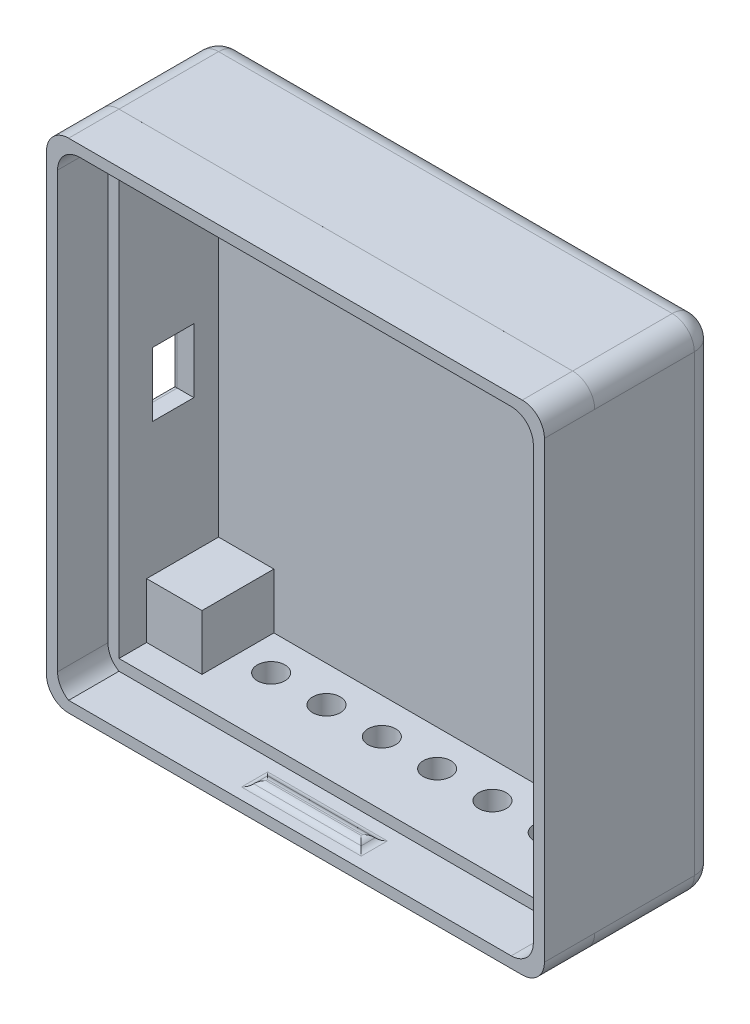
SolidWorks part; units mm, degrees
ref_plane "Piano frontale" through (0, 0, 0) normal (0, 0, 1) x (1, 0, 0)
ref_plane "Piano superiore" through (0, 0, 0) normal (0, 1, 0) x (1, 0, 0)
ref_plane "Piano destro" through (0, 0, 0) normal (1, 0, 0) x (0, 0, -1)
sketch "Schizzo2" plane through (0, 0, 0) normal (0, 0, 1) x (1, 0, 0)
  line L1 (0, 0) -> (45, 0)
  line L2 (0, 0) -> (0, 45)
  line L3 (0, 45) -> (45, 45)
  line L4 (45, 0) -> (45, 45)
  dimension "D1" = 45
  dimension "D2" = 45
extrude "Estrusione-Estrusione2" add sketch "Schizzo2" along normal blind 11
shell "Svuota1" thickness 2 removed face at (22.5, 22.5, 11)
fillet "Raccordo1" radius 2 4 edges at (45, 45, 5.5) (45, 0, 5.5) (0, 0, 5.5) (0, 45, 5.5)
fillet "Raccordo2" radius 2 8 edges at (44.4142, 0.5858, 0) (22.5, 0, 0) (0.5858, 0.5858, 0) (0, 22.5, 0) (0.5858, 44.4142, 0) (22.5, 45, 0) (44.4142, 44.4142, 0) (45, 22.5, 0)
sketch "Schizzo3" plane through (0, 0, 2) normal (0, 0, 1) x (1, 0, 0)
  line L0 (43, 43) -> (2, 43) construction
  line L1 (2, 43) -> (7, 43)
  line L2 (2, 43) -> (2, 38)
  line L3 (2, 38) -> (7, 38)
  line L4 (7, 43) -> (7, 38)
  line L5 (43, 43) -> (2, 43) construction
  dimension "D1" = 5
  dimension "D2" = 5
extrude "Estrusione-Estrusione3" add sketch "Schizzo3" along normal blind 6.5
sketch "Schizzo4" plane through (0, 0, 2) normal (0, 0, 1) x (1, 0, 0)
  line L1 (43, 2) -> (38, 2)
  line L2 (43, 2) -> (43, 7)
  line L3 (43, 7) -> (38, 7)
  line L4 (38, 2) -> (38, 7)
  dimension "D1" = 5
  dimension "D2" = 5
extrude "Estrusione-Estrusione4" add sketch "Schizzo4" along normal blind 6.5
fillet "Raccordo3" radius 4 2 edges at (38, 7, 5.25) (7, 38, 5.25)
sketch "Schizzo5" plane through (0, 0, 2) normal (0, 0, 1) x (1, 0, 0)
  line L0 (43, 2) -> (43, 43) construction
  line L1 (43, 43) -> (38, 43)
  line L2 (43, 43) -> (43, 38)
  line L3 (43, 38) -> (38, 38)
  line L4 (38, 43) -> (38, 38)
  line L5 (43, 43) -> (7, 43) construction
  line L7 (2, 2) -> (7, 2)
  line L8 (2, 2) -> (2, 7)
  line L9 (2, 7) -> (7, 7)
  line L10 (7, 2) -> (7, 7)
  dimension "D1" = 5
  dimension "D2" = 5
  dimension "D3" = 5
  dimension "D4" = 5
extrude "Estrusione-Estrusione5" add sketch "Schizzo5" along normal blind 6.5 contours L2 L1 L4 L3 | L8 L7 L10 L9
sketch "Schizzo7" plane through (0, 0, 0) normal (-1, 0, 0) x (0, 0, 1)
  line L1 (4.2347, 24.8244) -> (7.9559, 24.8244)
  line L2 (4.2347, 24.8244) -> (4.2347, 19.0329)
  line L3 (4.2347, 19.0329) -> (7.9559, 19.0329)
  line L4 (7.9559, 24.8244) -> (7.9559, 19.0329)
extrude "Taglio-Estrusione1" cut sketch "Schizzo7" against normal blind 3
sketch "Schizzo12" plane through (0, 0, 11) normal (0, 0, 1) x (1, 0, 0)
  line L1 (0, 44.9999) -> (45, 44.9999)
  line L2 (0, 44.9999) -> (0, 43.9999)
  line L3 (0, 43.9999) -> (45, 43.9999)
  line L4 (45, 44.9999) -> (45, 43.9999)
  dimension "D1" = 45
  dimension "D2" = 1
extrude "Estrusione-Estrusione7" add sketch "Schizzo12" along normal blind 4.55
sketch "Schizzo13" plane through (0, 0, 11) normal (0, 0, 1) x (1, 0, 0)
  line L1 (45, 43.9999) -> (44, 43.9999)
  line L2 (45, 43.9999) -> (45, -0.0001)
  line L3 (45, -0.0001) -> (44, -0.0001)
  line L4 (44, 43.9999) -> (44, -0.0001)
  dimension "D1" = 44
  dimension "D2" = 1
extrude "Estrusione-Estrusione10" add sketch "Schizzo13" along normal blind 4.55
sketch "Schizzo15" plane through (0, 0, 11) normal (0, 0, 1) x (1, 0, 0)
  line L1 (44, -0.0001) -> (2, -0.0001)
  line L2 (44, -0.0001) -> (44, 0.9999)
  line L3 (44, 0.9999) -> (2, 0.9999)
  line L4 (2, -0.0001) -> (2, 0.9999)
  dimension "D1" = 1
  dimension "D2" = 42
extrude "Estrusione-Estrusione11" add sketch "Schizzo15" along normal blind 4.55
fillet "Raccordo4" radius 2 1 edges at (45, -0.0001, 13.275)
fillet "Raccordo5" radius 2 1 edges at (45, 44.9999, 13.275)
sketch "Schizzo17" plane through (0, 0, 11) normal (0, 0, 1) x (1, 0, 0)
  line L1 (0, 43.9999) -> (1, 43.9999)
  line L2 (0, 43.9999) -> (0, -0.0001)
  line L3 (0, -0.0001) -> (1, -0.0001)
  line L4 (1, 43.9999) -> (1, -0.0001)
  dimension "D1" = 1
  dimension "D2" = 44
extrude "Estrusione-Estrusione13" add sketch "Schizzo17" along normal blind 4.55
fillet "Raccordo6" radius 2 1 edges at (0, 44.9999, 13.275)
fillet "Raccordo7" radius 2 1 edges at (44, 0.9999, 13.275)
fillet "Raccordo8" radius 2 1 edges at (44, 43.9999, 13.275)
fillet "Raccordo9" radius 2 1 edges at (1, 43.9999, 13.275)
sketch "Schizzo18" plane through (0, 0, 11) normal (0, 0, 1) x (1, 0, 0)
  line L0 (1, -0.0001) -> (1, 41.9999) construction
  line L1 (2, -0.0001) -> (1, -0.0001)
  line L2 (2, -0.0001) -> (2, 0.9995)
  line L3 (2, 0.9995) -> (1, 0.9995)
  line L4 (1, -0.0001) -> (1, 0.9995)
extrude "Estrusione-Estrusione14" add sketch "Schizzo18" along normal blind 4.55
fillet "Raccordo10" radius 2 1 edges at (0, -0.0001, 13.275)
fillet "Raccordo11" radius 2 1 edges at (1, 0.9995, 13.275)
fillet "Raccordo12" radius 0.5 4 edges at (0, 19.0329, 6.0953) (0, 21.9286, 7.9559) (0, 21.9286, 4.2347) (0, 24.8244, 6.0953)
sketch "Schizzo21" plane through (0, 2, 0) normal (0, 1, 0) x (1, 0, 0)
  circle A0 centre (10.0012, -5.25) radius 1.25
  circle A1 centre (15.004, -5.25) radius 1.25
  circle A2 centre (20.0048, -5.25) radius 1.25
  circle A3 centre (25.0045, -5.25) radius 1.25
  circle A4 centre (30.0037, -5.25) radius 1.25
  circle A5 centre (35.0006, -5.25) radius 1.25
  dimension "D1" = 2.5
  dimension "D2" = 2.5
  dimension "D3" = 2.5
  dimension "D4" = 2.5
  dimension "D5" = 2.5
  dimension "D6" = 2.5
extrude "Taglio-Estrusione4" cut sketch "Schizzo21" against normal blind 2
sketch "Schizzo22" plane through (0, 0.9999, 0) normal (0, 1, 0) x (1, 0, 0)
  line L5 (17.0049, -12.5647) -> (27.0049, -12.5647)
  line L6 (17.0049, -12.5647) -> (17.0049, -14.1147)
  line L7 (17.0049, -14.1147) -> (27.0049, -14.1147)
  line L8 (27.0049, -12.5647) -> (27.0049, -14.1147)
  dimension "D1" = 1.55
  dimension "D2" = 10
extrude "Estrusione-Estrusione15" add sketch "Schizzo22" along normal blind 0.5
fillet "Raccordo17" radius 0.74 4 edges at (27.0049, 1.4999, 13.3397) (22.0049, 1.4999, 12.5647) (17.0049, 1.4999, 13.3397) (22.0049, 1.4999, 14.1147)
fillet "Raccordo18" radius 0.74 4 edges at (22.0049, 0.9999, 12.5647) (27.0049, 0.9999, 13.3397) (17.0049, 0.9999, 13.3397) (22.0049, 0.9999, 14.1147)
sketch "Schizzo30" plane through (0, 43.9999, 0) normal (0, -1, 0) x (1, 0, 0)
  line L1 (17.0049, 14.1147) -> (27.0049, 14.1147)
  line L2 (17.0049, 14.1147) -> (17.0049, 12.5647)
  line L3 (17.0049, 12.5647) -> (27.0049, 12.5647)
  line L4 (27.0049, 14.1147) -> (27.0049, 12.5647)
extrude "Estrusione-Estrusione20" add sketch "Schizzo30" along normal blind 0.5 draft 1
fillet "Raccordo19" radius 0.74 4 edges at (22.0049, 43.4999, 12.5735) (26.9962, 43.4999, 13.3397) (22.0049, 43.4999, 14.106) (17.0136, 43.4999, 13.3397)
fillet "Raccordo20" radius 0.74 4 edges at (17.0049, 43.9999, 13.3397) (22.0049, 43.9999, 12.5647) (27.0049, 43.9999, 13.3397) (22.0049, 43.9999, 14.1147)
